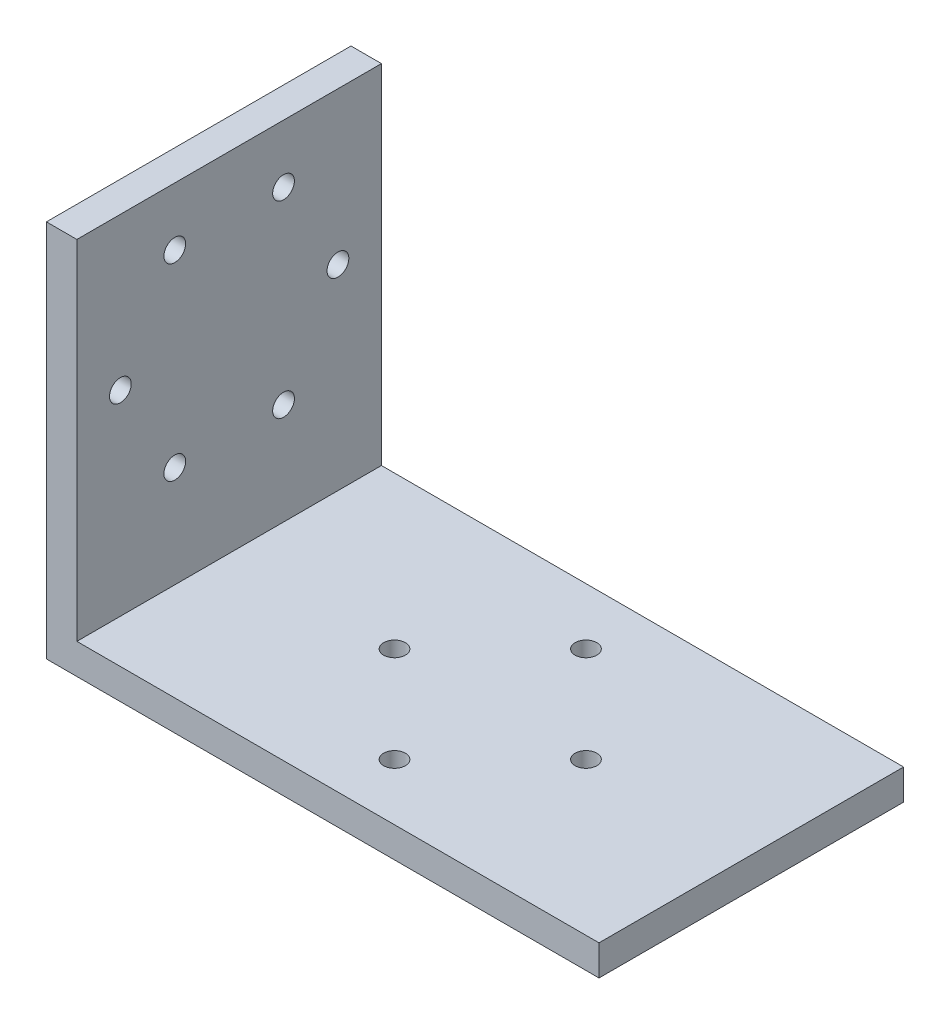
SolidWorks part; units mm, degrees
ref_plane "前视基准面" through (0, 0, 0) normal (0, 0, 1) x (1, 0, 0)
ref_plane "上视基准面" through (0, 0, 0) normal (0, 1, 0) x (1, 0, 0)
ref_plane "右视基准面" through (0, 0, 0) normal (1, 0, 0) x (0, 0, -1)
sketch "草图1" plane through (0, 0, 0) normal (0, 1, 0) x (1, 0, 0)
  line L1 (0, 0) -> (120, 0)
  line L2 (0, 0) -> (0, 70)
  line L3 (0, 70) -> (120, 70)
  line L4 (120, 0) -> (120, 70)
extrude "凸台-拉伸1" add sketch "草图1" along normal blind 7
sketch "草图2" plane through (0, 7, 0) normal (0, 1, 0) x (1, 0, 0)
  circle A0 centre (82, 35) radius 2.5
  circle A1 centre (60, 13) radius 2.5
  circle A2 centre (38, 35) radius 2.5
  circle A3 centre (60, 57) radius 2.5
  point P12 (60, 35)
  dimension "D1" = 4
extrude "切除-拉伸2" cut sketch "草图2" against normal blind 7 contours A2 | A1 | A0 | A3
sketch "草图5" plane through (0, 0, 0) normal (-1, 0, 0) x (0, 0, 1)
  line L1 (-70, 0) -> (0, 0)
  line L2 (-70, 0) -> (-70, 87)
  line L3 (-70, 87) -> (0, 87)
  line L4 (0, 0) -> (0, 87)
extrude "凸台-拉伸4" add sketch "草图5" along normal blind 7
sketch "草图6" plane through (-7, 0, 0) normal (-1, 0, 0) x (0, 0, 1)
  circle A0 centre (-10, 52) radius 2.5
  circle A1 centre (-22.5, 30.3494) radius 2.5
  circle A2 centre (-47.5, 30.3494) radius 2.5
  circle A3 centre (-60, 52) radius 2.5
  circle A4 centre (-47.5, 73.6506) radius 2.5
  circle A5 centre (-22.5, 73.6506) radius 2.5
  point P18 (-35, 52)
  dimension "D1" = 6
extrude "切除-拉伸3" cut sketch "草图6" against normal blind 7
